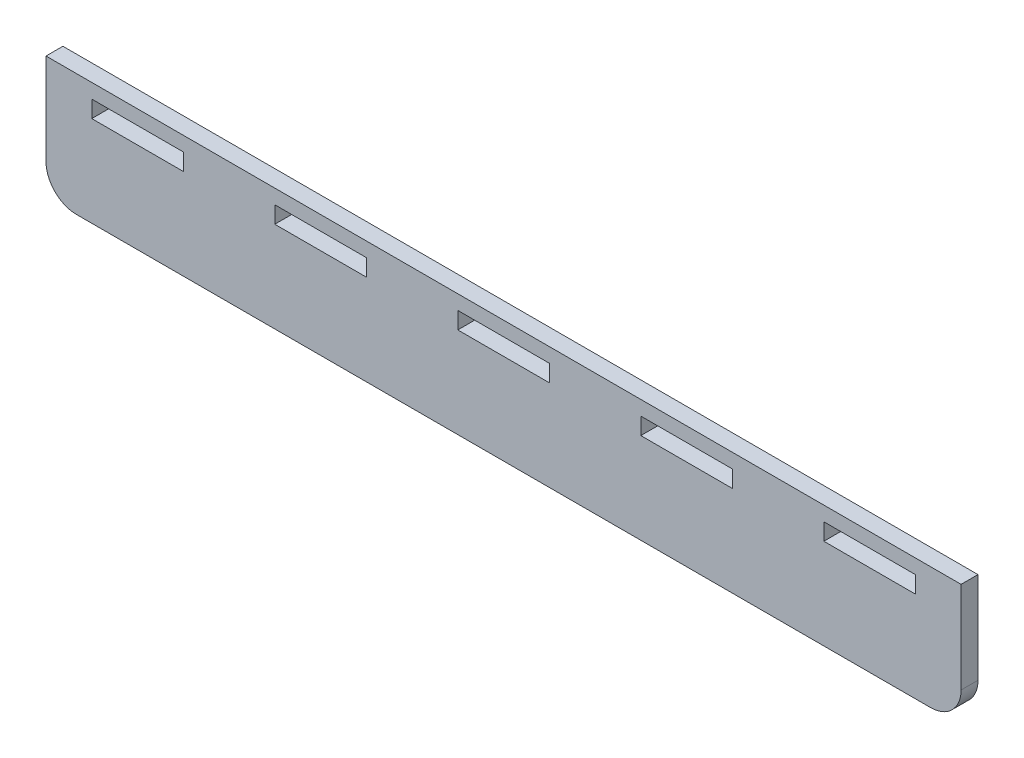
SolidWorks part; units mm, degrees
ref_plane "Front Plane" through (0, 0, 0) normal (0, 0, 1) x (1, 0, 0)
ref_plane "Top Plane" through (0, 0, 0) normal (0, 1, 0) x (1, 0, 0)
ref_plane "Right Plane" through (0, 0, 0) normal (1, 0, 0) x (0, 0, -1)
sketch "Sketch2" plane through (0, 0, 0) normal (0, 0, 1) x (1, 0, 0)
  line L5 (34.1639, 15.146) -> (119.4339, 15.146)
  line L35 (59.4746, 0.146) -> (59.4746, 15.146)
  line L40 (34.2026, 0.146) -> (111.0965, 0.146)
  line L57 (29.4339, 10.416) -> (34.1639, 15.146)
  line L58 (29.4746, 4.876) -> (34.2026, 0.146)
  line L62 (74.4746, 10.416) -> (74.4746, 4.876)
  line L63 (74.4746, 10.416) -> (104.4746, 10.416)
  line L64 (104.4746, 10.416) -> (104.4746, 4.876)
  line L65 (74.4746, 4.876) -> (104.4746, 4.876)
  line L66 (314.4746, 10.416) -> (314.4746, 4.876)
  line L67 (29.4746, 4.876) -> (44.4746, 4.876)
  line L69 (29.4339, 10.416) -> (44.4746, 10.416)
  line L70 (44.4746, 4.876) -> (44.4746, 10.416)
  line L75 (59.4746, 0.146) -> (359.4746, 0.146)
  line L76 (134.4746, 10.416) -> (134.4746, 4.876)
  line L77 (134.4746, 4.876) -> (164.4746, 4.876)
  line L78 (164.4746, 10.416) -> (164.4746, 4.876)
  line L79 (134.4746, 10.416) -> (164.4746, 10.416)
  line L80 (194.4746, 10.416) -> (194.4746, 4.876)
  line L81 (194.4746, 4.876) -> (224.4746, 4.876)
  line L82 (224.4746, 10.416) -> (224.4746, 4.876)
  line L83 (194.4746, 10.416) -> (224.4746, 10.416)
  line L84 (254.4746, 10.416) -> (254.4746, 4.876)
  line L85 (254.4746, 4.876) -> (284.4746, 4.876)
  line L86 (284.4746, 10.416) -> (284.4746, 4.876)
  line L87 (254.4746, 10.416) -> (284.4746, 10.416)
  line L88 (209.4746, 45.3214) -> (209.4746, -24.4893) construction
  line L90 (59.4746, 0.146) -> (59.4746, -24.854)
  line L91 (374.4746, 4.876) -> (374.4746, 10.416)
  line L92 (389.5153, 10.416) -> (374.4746, 10.416)
  line L93 (389.4746, 4.876) -> (374.4746, 4.876)
  line L94 (59.4746, -24.854) -> (359.4746, -24.854)
  line L95 (389.4746, 4.876) -> (384.7466, 0.146)
  line L96 (389.5153, 10.416) -> (384.7853, 15.146)
  line L97 (384.7466, 0.146) -> (307.8527, 0.146)
  line L98 (384.7853, 15.146) -> (299.5153, 15.146)
  line L99 (119.4339, 15.146) -> (299.5153, 15.146)
  line L100 (111.0965, 0.146) -> (307.8527, 0.146)
  line L101 (359.4746, 0.146) -> (359.4746, -24.854)
  line L102 (314.4746, 4.876) -> (344.4746, 4.876)
  line L103 (344.4746, 10.416) -> (344.4746, 4.876)
  line L104 (314.4746, 10.416) -> (344.4746, 10.416)
  line L109 (359.4746, 0.146) -> (359.4746, 15.146)
  point P0 (29.4339, 15.146)
  point P2 (29.4726, 0.146)
  point P30 (209.4746, 10.416)
  point P31 (389.4766, 0.146)
  point P32 (389.5153, 15.146)
  dimension "D2" = 15
  dimension "D3" = 5
  dimension "D4" = 25
  dimension "D5" = 15
  dimension "D6" = 15
  dimension "D8" = 30
  dimension "D9" = 30
  dimension "D10" = 5.54
  dimension "D11" = 30
  dimension "D7" = 15
extrude "Boss-Extrude1" add sketch "Sketch2" along normal blind 5.54 contours L101 L75 L100 L40 L90 L94 | L88 L99 L5 L35 L40 L75 L81 L80 L83 L65 L62 L63 L64 L76 L79 L78 L77 | L99 L88 L83 L82 L81 L100 L75 L109 L98 L66 L104 L103 L102 L84 L87 L86 L85 region at (134.1349, 7.646, 0) region at (85.2856, -2.8644, 0) region at (284.8143, 7.646, 0)
fillet "Fillet1" radius 10 2 edges at (359.4746, -24.854, 2.77) (59.4746, -24.854, 2.77)
